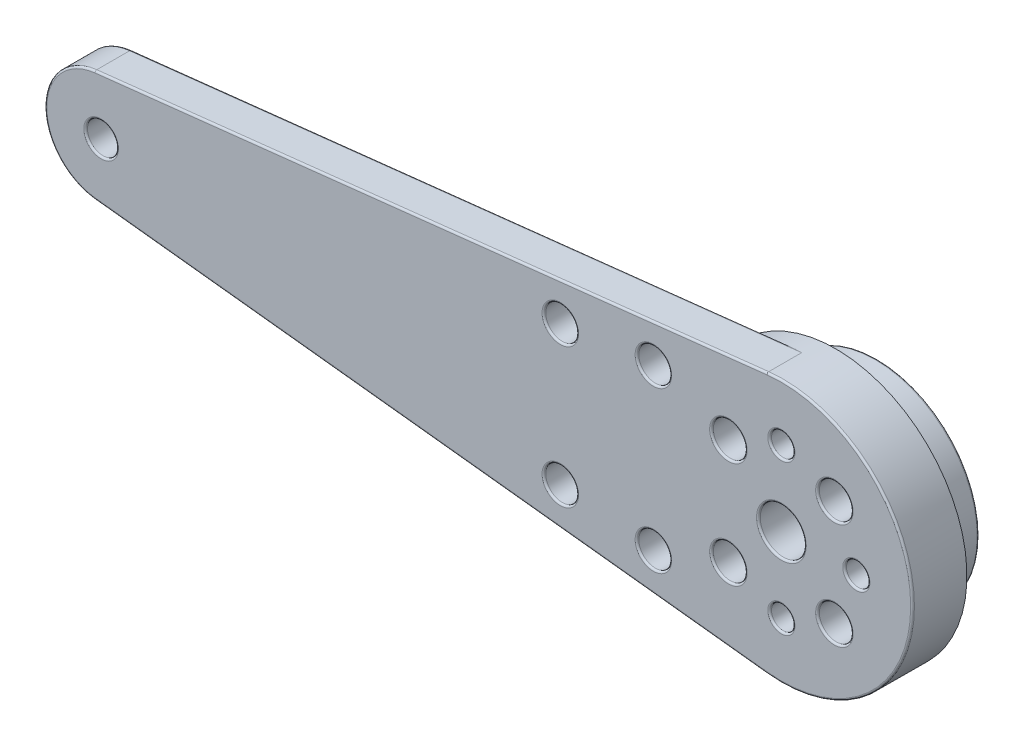
SolidWorks part; units mm, degrees
ref_plane "정면" through (0, 0, 0) normal (0, 0, 1) x (1, 0, 0)
ref_plane "윗면" through (0, 0, 0) normal (0, 1, 0) x (1, 0, 0)
ref_plane "우측면" through (0, 0, 0) normal (1, 0, 0) x (0, 0, -1)
sketch "스케치1" plane through (0, 0, 0) normal (0, 0, 1) x (1, 0, 0)
  line L0 (0, 0) -> (5.6569, 5.6569) construction
  line L1 (0, 0) -> (9.1372, 0) construction
  line L2 (0, 0) -> (-72.59, 0) construction
  line L3 (-73.2512, 5.9635) -> (-1.5429, 13.9147)
  line L4 (-73.2512, -5.9635) -> (-1.5429, -13.9147)
  line L5 (-27.59, 11.0265) -> (-27.59, -11.0265) construction
  line L6 (-9.6569, 13.015) -> (-9.6569, -13.015) construction
  arc A0 (-1.5429, -13.9147) -> (-1.5429, 13.9147) centre (0, 0) ccw
  circle A1 centre (5.6569, 5.6569) radius 1.8
  circle A2 centre (5.6569, -5.6569) radius 1.8
  circle A3 centre (-5.6569, -5.6569) radius 1.8
  circle A4 centre (-5.6569, 5.6569) radius 1.8
  circle A5 centre (0, 0) radius 4
  arc A6 (-73.2512, 5.9635) -> (-73.2512, -5.9635) centre (-72.59, 0) ccw
  circle A7 centre (-72.59, 0) radius 1.65
  circle A8 centre (0, 0) radius 10.9
  circle A10 centre (-23.59, 7.4455) radius 1.75
  circle A12 centre (-13.6569, 8.547) radius 1.75
  circle A13 centre (-13.6569, -8.547) radius 1.75
  circle A14 centre (-23.59, -7.4455) radius 1.75
  point P15 (0, 0)
  dimension "D1" = 28
  dimension "D3" = 3.6
  dimension "D6" = 8
  dimension "D8" = 12
  dimension "D9" = 3.3
  dimension "D10" = 21.8
  dimension "D13" = 3.5
  dimension "D14" = 3.5
  dimension "D2" = 45
  dimension "D4" = 8
  dimension "D7" = 72.59
  dimension "D11" = 45
  dimension "D12" = 4
  dimension "D15" = 4
  dimension "D16" = 4
  dimension "D17" = 4
  dimension "D18" = 4
  dimension "D5" = 4
extrude "보스-돌출1" add sketch "스케치1" along normal blind 3.9 contours L3 A6 L4 L5 A7 | L4 A0 L3 L5 A8 | A8 A1 A2 A3 A4 A5 | A5 region at (-49.5265, 0, 0) region at (-11.2475, 0, 0) region at (0, 0, 0) region at (-10.5917, 0, 0)
extrude "보스-돌출2" add sketch "스케치1<6>" against normal blind 6.3 contours A8 A1 A2 A3 A4 A5 | A5 region at (0, 0, 0) region at (-10.5917, 0, 0)
sketch "스케치1<6>" plane through (0, 0, 0) normal (0, 0, 1) x (1, 0, 0) same geometry as "스케치1"
sketch "스케치2" plane through (0, 0, 3.9) normal (0, 0, 1) x (1, 0, 0)
  line L0 (-27.59, 11.0265) -> (-27.59, -11.0265) construction
  line L1 (0, 0) -> (-38.7117, 0) construction
  line L2 (-1.5429, 13.9147) -> (-73.2512, 5.9635)
  line L3 (-73.2512, -5.9635) -> (-1.5429, -13.9147)
  line L4 (-1.5429, 13.9147) -> (-73.2512, 5.9635)
  line L5 (-73.2512, -5.9635) -> (-1.5429, -13.9147)
  line L7 (-12, 12.7552) -> (-12, -12.7552) construction
  line L8 (-12, 12.7552) -> (-8.834, 4.4463) construction
  line L9 (-12, -12.7552) -> (-8.834, -4.4463) construction
  arc A2 (-73.2512, 5.9635) -> (-73.2512, -5.9635) centre (-72.59, 0) ccw
  arc A3 (-1.5429, -13.9147) -> (-1.5429, 13.9147) centre (0, 0) ccw
  arc A4 (-73.2512, 5.9635) -> (-73.2512, -5.9635) centre (-72.59, 0) ccw
  arc A5 (-1.5429, -13.9147) -> (-1.5429, 13.9147) centre (0, 0) ccw
  circle A7 centre (-5.6569, 5.6569) radius 3.4
  circle A8 centre (-5.6569, -5.6569) radius 3.4
  circle A9 centre (-7.75, 0) radius 2.6317
  circle A10 centre (-7.75, 0) radius 1.65
  circle A13 centre (5.6569, 5.6569) radius 3.4
  circle A14 centre (5.6569, -5.6569) radius 3.4
  circle A15 centre (0, 7.75) radius 2.6317
  circle A16 centre (7.75, 0) radius 2.6317
  circle A17 centre (0, -7.75) radius 2.6317
  circle A18 centre (0, 7.75) radius 1.65
  circle A19 centre (7.75, 0) radius 1.65
  circle A20 centre (0, -7.75) radius 1.65
  dimension "D6" = 6.8
  dimension "D7" = 3.3
  dimension "D2" = 45
  dimension "D8" = 7.75
  dimension "D9" = 12
  dimension "D12" = 7.75
  dimension "D13" = 7.75
  dimension "D14" = 7.75
  dimension "D1" = 0
sketch "스케치3" plane through (0, 0, 0) normal (0, 0, -1) x (-1, 0, 0)
  circle A0 centre (0, 0) radius 14
  circle A1 centre (0, 0) radius 10.9 construction
  circle A2 centre (0, 0) radius 10.9
  circle M5 centre (0, 0) radius 10.9
  arc M8 (1.5429, 13.9147) -> (1.5429, -13.9147) centre (0, 0) ccw
  dimension "D1" = 28
extrude "보스-돌출3" add sketch "스케치3" along normal blind 1.9 contours A0 M8 M5 region at (-10.1357, -9.074, 0)
sketch "스케치4" plane through (0, 0, -6.3) normal (0, 0, -1) x (-1, 0, 0)
  circle A0 centre (0, 0) radius 2.45
  dimension "D1" = 4.9
extrude "컷-돌출2" cut sketch "스케치4" against normal through all
sketch "스케치5" plane through (0, 0, 3.9) normal (0, 0, 1) x (1, 0, 0)
  line L0 (0, 14) -> (0, -14) construction
  line L1 (0, 0) -> (9.1372, 0) construction
  arc A0 (-1.5429, -13.9147) -> (-1.5429, 13.9147) centre (0, 0) ccw construction
  circle A2 centre (0, 8) radius 1.25
  circle A4 centre (0, -8) radius 1.25
  circle A6 centre (8, 0) radius 1.25
  dimension "D2" = 2.5
  dimension "D5" = 2.5
  dimension "D8" = 2.5
  dimension "D3" = 8
  dimension "D6" = 8
  dimension "D9" = 8
extrude "컷-돌출3" cut sketch "스케치5" against normal through all contours A2 | A6 | A4
fillet "필렛2" radius 0.2 26 edges at (10.9, 0, -6.3) (7.4569, 5.6569, -6.3) (7.4569, -5.6569, -6.3) (-3.8569, -5.6569, -6.3) (-3.8569, 5.6569, -6.3) (-2.45, 0, -6.3) (1.25, -8, -6.3) (9.25, 0, -6.3) (1.25, 8, -6.3) (7.4569, 5.6569, 3.9) (7.4569, -5.6569, 3.9) (-3.8569, -5.6569, 3.9) (-3.8569, 5.6569, 3.9) (-21.84, -7.4455, 3.9) (14, 0, 3.9) (-37.3971, -9.9391, 3.9) (-78.59, 0, 3.9) (-37.3971, 9.9391, 3.9) (-70.94, 0, 3.9) (-21.84, 7.4455, 3.9) (-11.9069, 8.547, 3.9) (-11.9069, -8.547, 3.9) (-2.45, 0, 3.9) (1.25, -8, 3.9) (9.25, 0, 3.9) (1.25, 8, 3.9)
fillet "필렛3" radius 0.2 8 edges at (-37.3971, -9.9391, 0) (-78.59, 0, 0) (-70.94, 0, 0) (-37.3971, 9.9391, 0) (-11.9069, 8.547, 0) (-21.84, 7.4455, 0) (-11.9069, -8.547, 0) (-21.84, -7.4455, 0)
